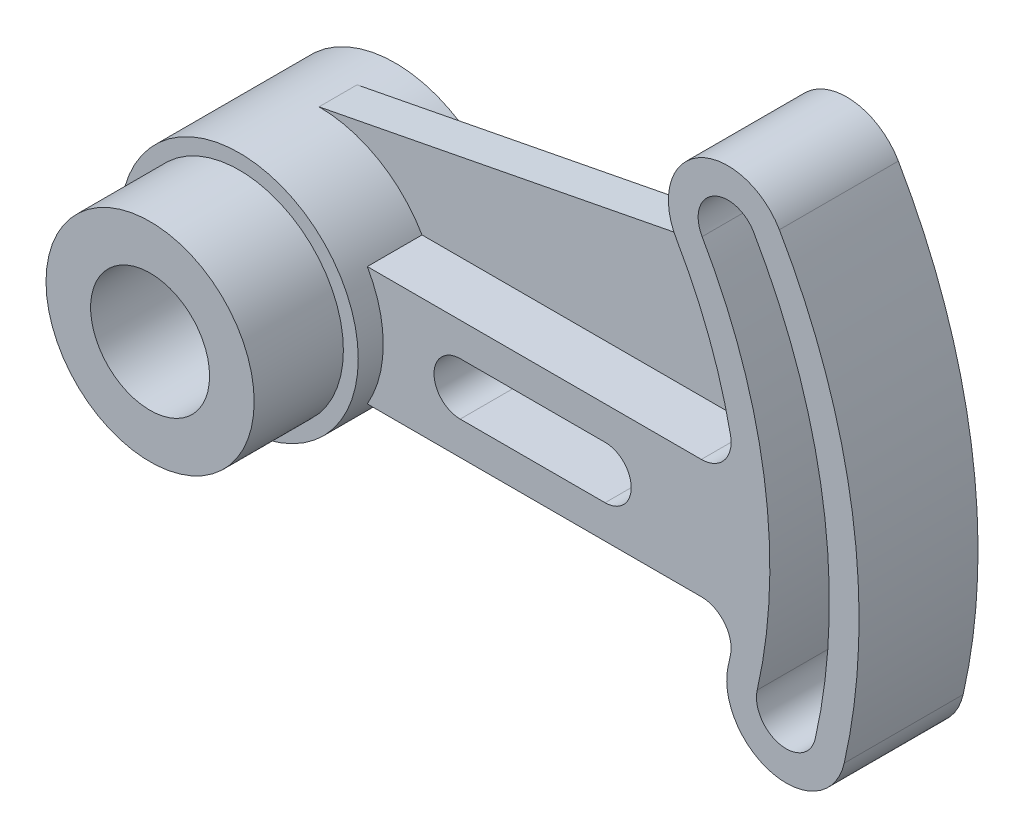
SolidWorks part; units mm, degrees
ref_plane "Front Plane" through (0, 0, 0) normal (0, 0, 1) x (1, 0, 0)
ref_plane "Top Plane" through (0, 0, 0) normal (0, 1, 0) x (1, 0, 0)
ref_plane "Right Plane" through (0, 0, 0) normal (1, 0, 0) x (0, 0, -1)
sketch "Sketch1" plane through (0, 0, 0) normal (0, 0, 1) x (1, 0, 0)
  circle A0 centre (0, 0) radius 25.4
extrude "Boss-Extrude2" add sketch "Sketch1" along normal blind 33.274
sketch "Sketch2" plane through (0, 0, 33.274) normal (0, 0, 1) x (1, 0, 0)
  circle A0 centre (0, 0) radius 22.225
extrude "Boss-Extrude3" add sketch "Sketch2" along normal blind 19.05
sketch "Sketch3" plane through (0, 0, 0) normal (0, 0, 1) x (1, 0, 0)
  circle A0 centre (0, 0) radius 12.7
extrude "Cut-Extrude1" cut sketch "Sketch3" along normal through all
ref_plane "Plane1" through (0, 0, 2.54) normal (0, 0, 1) x (1, 0, 0)
sketch "Sketch6" plane through (0, 0, 2.54) normal (0, 0, 1) x (1, 0, 0)
  line L0 (0, 0) -> (109.9852, 63.5) construction
  line L1 (0, -25.4) -> (111.442, -25.4) construction
  line L2 (21.997, 12.7) -> (100.8031, 12.7)
  line L3 (21.997, -12.7) -> (100.8031, -12.7)
  line L4 (0, 0) -> (282.3895, 0) construction
  circle A0 centre (0, 0) radius 114.3 construction
  arc A1 (109.9852, 63.5) -> (87.9882, 50.8) centre (98.9867, 57.15) ccw
  arc A2 (99.0596, -22.5778) -> (123.8245, -28.2222) centre (111.442, -25.4) ccw
  arc A3 (87.9882, 50.8) -> (100.8031, 12.7) centre (0, 0) cw
  arc A4 (109.9852, 63.5) -> (123.8245, -28.2222) centre (0, 0) cw
  circle A5 centre (0, 0) radius 25.4 construction
  circle A6 centre (0, 0) radius 25.4
  arc A7 (100.8031, -12.7) -> (99.0596, -22.5778) centre (0, 0) cw
  arc A8 (21.997, 12.7) -> (21.997, -12.7) centre (0, 0) ccw
  dimension "D2" = 12.7
  dimension "D3" = 25.4
  dimension "D5" = 228.6
  dimension "D1" = 25.4
  dimension "D4" = 12.7
extrude "Boss-Extrude4" add sketch "Sketch6" along normal blind 25.4 contours L3 A7 A2 A4 A1 A3 L2 A8
fillet "Fillet1" radius 6.35 2 edges at (100.8031, -12.7, 15.24) (100.8031, 12.7, 15.24)
sketch "Sketch7" plane through (0, 0, 2.54) normal (0, 0, 1) x (1, 0, 0)
  line L0 (0, 0) -> (129.9241, 0) construction
  line L1 (41.8341, -5.588) -> (72.7665, -5.588)
  line L2 (41.8341, 5.588) -> (72.7665, 5.588)
  arc A0 (41.8341, 5.588) -> (41.8341, -5.588) centre (41.8341, 0) ccw
  arc A1 (72.7665, -5.588) -> (72.7665, 5.588) centre (72.7665, 0) ccw
  arc A4 (99.0596, -22.5778) -> (123.8245, -28.2222) centre (111.442, -25.4) ccw construction
  arc A6 (98.9867, 57.15) -> (111.442, -25.4) centre (0, 0) cw construction
  arc A7 (117.6333, -26.8111) -> (104.486, 60.325) centre (0, 0) ccw
  arc A8 (105.2508, -23.9889) -> (93.4874, 53.975) centre (0, 0) ccw
  arc A9 (105.2508, -23.9889) -> (117.6333, -26.8111) centre (111.442, -25.4) ccw
  arc A10 (104.486, 60.325) -> (93.4874, 53.975) centre (98.9867, 57.15) ccw
  point P18 (113.0208, 17.0528)
  dimension "D1" = 11.176
extrude "Cut-Extrude3" cut sketch "Sketch7" along normal through all
ref_plane "Plane2" through (0, 0, 8.128) normal (0, 0, 1) x (1, 0, 0)
sketch "Sketch8" plane through (0, 0, 8.128) normal (0, 0, 1) x (1, 0, 0)
  line L0 (21.997, 12.7) -> (93.3256, 12.7) construction
  line L1 (21.997, 12.7) -> (93.3256, 12.7)
  line L2 (0, 25.4) -> (91.926, 43.2686)
  arc A0 (99.5473, 20.32) -> (87.9882, 50.8) centre (0, 0) ccw construction
  arc A1 (93.3256, 12.7) -> (99.5473, 20.32) centre (93.3256, 19.05) ccw construction
  circle A2 centre (0, 0) radius 25.4 construction
  arc A3 (99.5473, 20.32) -> (91.926, 43.2686) centre (0, 0) ccw
  arc A4 (93.3256, 12.7) -> (99.5473, 20.32) centre (93.3256, 19.05) ccw
  arc A5 (21.997, 12.7) -> (0, 25.4) centre (0, 0) ccw
extrude "Boss-Extrude5" add sketch "Sketch8" along normal blind 8.128
fillet "Fillet2" radius 6.35 1 edges at (91.926, 43.2686, 12.192)
